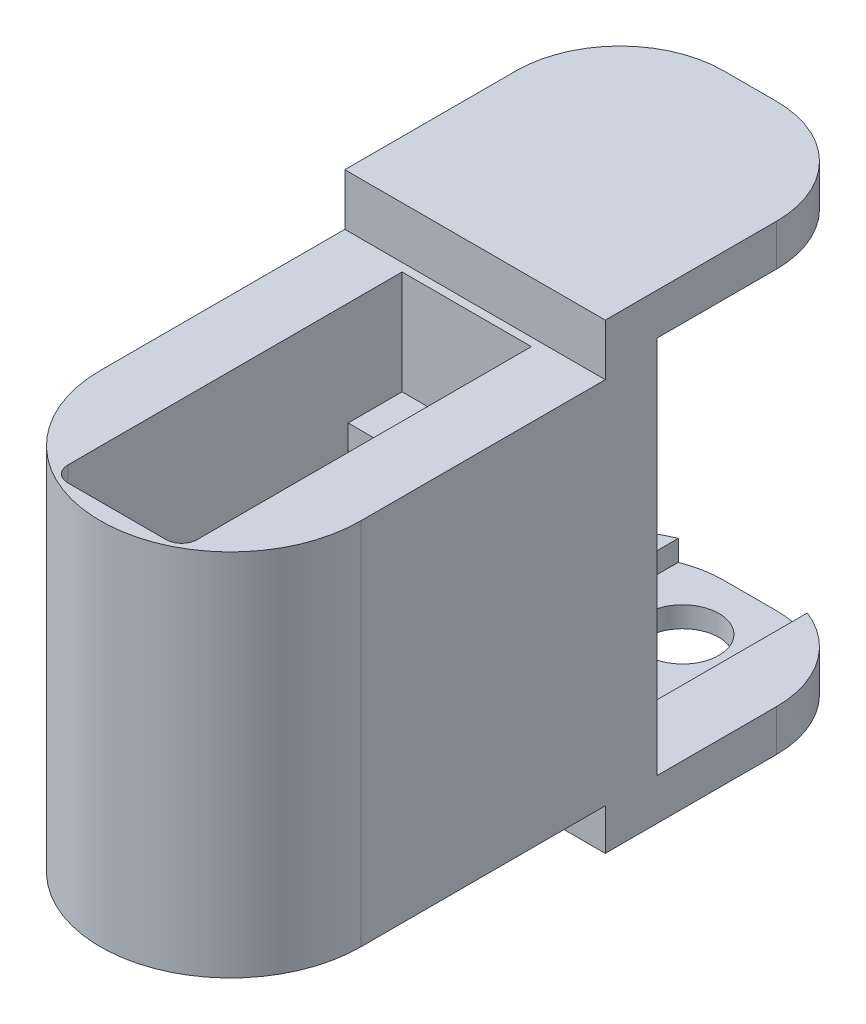
SolidWorks part; units mm, degrees
ref_plane "Front Plane" through (0, 0, 0) normal (0, 0, 1) x (1, 0, 0)
ref_plane "Top Plane" through (0, 0, 0) normal (0, 1, 0) x (1, 0, 0)
ref_plane "Right Plane" through (0, 0, 0) normal (1, 0, 0) x (0, 0, -1)
sketch "Sketch4" plane through (0, 0, 0) normal (0, 0, 1) x (1, 0, 0)
  line L1 (-6.23, -9.975) -> (6.23, -9.975)
  line L2 (-6.23, -9.975) -> (-6.23, 7.275)
  line L3 (-6.23, 7.275) -> (6.23, 7.275)
  line L4 (6.23, -9.975) -> (6.23, 7.275)
  point P4 (0, 7.275)
  dimension "D1" = 12.46
  dimension "D2" = 17.25
  dimension "D3" = 9.975
extrude "Boss-Extrude3" add sketch "Sketch4" along normal blind 6
sketch "Sketch8" plane through (0, -9.975, 0) normal (0, -1, 0) x (-1, 0, 0)
  circle A0 centre (0, -23.55) radius 12.5468
  circle A1 centre (0, -23.55) radius 11.15
  dimension "D1" = 22.3
  dimension "D2" = 23.55
extrude "Boss-Extrude6" add sketch "Sketch8" along normal blind 8.3 and the other way up to surface (17.25 mm away) other way up to face at (0, 7.275, 3)
sketch "Sketch5" plane through (0, 7.275, 0) normal (0, 1, 0) x (1, 0, 0)
  line L8 (12.5468, -23.55) -> (12.5468, 0)
  line L9 (12.5468, 0) -> (6.23, 0)
  line L10 (-12.5468, -23.55) -> (-12.5468, 0)
  line L11 (-12.5468, 0) -> (-6.23, 0)
  line L12 (-6.23, 0) -> (-6.23, -29.7)
  line L14 (6.23, -29.7) -> (6.23, 0)
  line L15 (-6.23, -29.7) -> (6.23, -29.7)
  line L16 (6.23, -6) -> (-6.23, -6) construction
  circle A0 centre (0, -23.55) radius 12.5468 construction
  arc A1 (-12.5468, -23.55) -> (12.5468, -23.55) centre (0, -23.55) ccw
  dimension "D1" = 23.7
  dimension "D2" = 23.55
extrude "Boss-Extrude4" add sketch "Sketch5" against normal up to surface (17.25 mm away) up to face at (0, -9.975, 3)
sketch "Sketch6" plane through (0, 7.275, 0) normal (0, 1, 0) x (1, 0, 0)
  line L0 (6.23, -6) -> (-6.23, -6) construction
  line L3 (6.23, -29.7) -> (-6.23, -29.7) construction
  circle A0 centre (0, -3.6) radius 0.75
  circle A1 centre (0, -32.1) radius 0.75
  dimension "D1" = 1.5
  dimension "D3" = 1.5
  dimension "D2" = 2.4
  dimension "D4" = 2.4
extrude "Cut-Extrude1" cut sketch "Sketch6" against normal blind 5
chamfer "Chamfer1" distance 0.5 angle 60 2 edges at (0, 7.275, 4.35) (0, 7.275, 32.85) first distance on face at (0, 7.275, 4.35)
sketch "Sketch10" plane through (0, 7.275, 0) normal (0, 1, 0) x (1, 0, 0)
  line L1 (-6.23, -6) -> (6.23, -6)
  line L2 (-6.23, -6) -> (-6.23, -29.7)
  line L3 (-6.23, -29.7) -> (6.23, -29.7)
  line L4 (6.23, -6) -> (6.23, -29.7)
extrude "Cut-Extrude3" cut sketch "Sketch10" against normal up to surface (17.25 mm away) up to face at (0, -9.975, 10.3399)
ref_plane "Plane1" through (0, 0, 36.0968) normal (0, 0, 1) x (1, 0, 0)
sketch "Sketch13" plane through (0, -18.275, 0) normal (0, -1, 0) x (1, 0, 0)
  line L0 (-12.5468, 23.55) -> (-12.5468, 0)
  line L1 (-12.5468, 0) -> (12.5468, 0)
  line L2 (12.5468, 0) -> (12.5468, 23.55)
  arc A0 (-12.5468, 23.55) -> (12.5468, 23.55) centre (0, 23.55) ccw
  point P3 (0, 0)
extrude "Boss-Extrude7" add sketch "Sketch13" against normal up to surface (8.3 mm away) up to face at (0, -9.975, 10.3399)
sketch "Sketch15" plane through (0, 7.275, 0) normal (0, 1, 0) x (1, 0, 0)
  line L0 (-12.5468, 0) -> (12.5468, 0)
  line L1 (12.5468, 0) -> (12.5468, -23.55)
  line L2 (-12.5468, 0) -> (-12.5468, -23.55)
  line L3 (6.23, -6) -> (6.23, -29.7) construction
  line L4 (-6.23, -0.8) -> (6.23, -0.8)
  line L5 (-6.23, -0.8) -> (-6.23, -33)
  line L6 (-4.73, -34.5) -> (4.73, -34.5)
  line L7 (6.23, -0.8) -> (6.23, -33)
  arc A0 (-12.5468, -23.55) -> (12.5468, -23.55) centre (0, -23.55) ccw
  circle A1 centre (0, -3.6) radius 0.75 construction
  arc A2 (4.73, -34.5) -> (6.23, -33) centre (4.73, -33) ccw
  arc A3 (-6.23, -33) -> (-4.73, -34.5) centre (-4.73, -33) ccw
  point P15 (0, -0.8)
  dimension "D1" = 0.8
  dimension "D3" = 1.5
  dimension "D2" = 2.8
  dimension "D4" = 0
  dimension "D5" = 34.5
extrude "Boss-Extrude9" add sketch "Sketch15" along normal blind 10
sketch "Sketch20" plane through (0, -18.275, 0) normal (0, -1, 0) x (1, 0, 0)
  circle A0 centre (0, 23.55) radius 7.15
  circle A1 centre (0, 23.55) radius 11.15
  circle A2 centre (0, 23.55) radius 11.15 construction
  dimension "D1" = 14.3
extrude "Boss-Extrude11" add sketch "Sketch20" against normal up to surface (8.3 mm away) up to face at (0, -9.975, 27.1007)
sketch "Sketch21" plane through (0, -18.275, 0) normal (0, -1, 0) x (1, 0, 0)
  circle A0 centre (0, 23.55) radius 7.15
  circle A1 centre (0, 23.55) radius 10.15
  circle A2 centre (0, 23.55) radius 7.15 construction
  dimension "D1" = 20.3
extrude "Cut-Extrude7" cut sketch "Sketch21" against normal blind 1.3
sketch "Sketch11" plane through (0, 0, 29.7) normal (0, 0, 1) x (1, 0, 0)
  line L1 (-5, -9.975) -> (5, -9.975)
  line L2 (-5, -9.975) -> (-5, -11.975)
  line L3 (-5, -11.975) -> (5, -11.975)
  line L4 (5, -9.975) -> (5, -11.975)
  line L5 (3.6469, -9.975) -> (6.23, -9.975) construction
  point P4 (0, -9.975)
  dimension "D1" = 0
  dimension "D2" = 10
  dimension "D3" = 2
extrude "Cut-Extrude4" cut sketch "Sketch11" against normal up to surface (23.7 mm away) up to face at (0, -1.35, 6)
sketch "Sketch17" plane through (-12.5468, 4.7282, 0) normal (1, 0, 0) x (0, -1, 0)
  line L0 (26.9782, 26.5) -> (26.9782, 0)
  line L1 (26.9782, 0) -> (-17.5218, 0)
  line L2 (-17.5218, 0) -> (-17.5218, 26.5)
  line L3 (-17.5218, 26.5) -> (-13.5218, 26.5)
  line L4 (-13.5218, 26.5) -> (-13.5218, 5)
  line L5 (-13.5218, 5) -> (22.9782, 5)
  line L6 (22.9782, 5) -> (22.9782, 26.5)
  line L7 (22.9782, 26.5) -> (26.9782, 26.5)
  point P2 (4.7282, 5)
  point P10 (4.7282, 0)
  dimension "D1" = 4
  dimension "D2" = 36.5
  dimension "D3" = 0
  dimension "D4" = 26.5
  dimension "D5" = 5
extrude "Boss-Extrude10" add sketch "Sketch17" along normal up to surface (25.0936 mm away) up to face at (12.5468, -0.5, 11.775)
sketch "Sketch18" plane through (0, -18.25, 0) normal (0, 1, 0) x (0, 0, 1)
  line L0 (-26.5, -12.5468) -> (-26.5, 12.5468) construction
  line L1 (-26.5, 6.2191) -> (-5, 6.2191)
  line L2 (-26.5, 6.2191) -> (-26.5, -6.2191)
  line L3 (-26.5, -6.2191) -> (-5, -6.2191)
  line L4 (-5, 6.2191) -> (-5, -6.2191)
  line L5 (-5, -12.5468) -> (-5, 12.5468) construction
  point P6 (-26.5, 0)
  point P7 (-26.5, 0)
  dimension "D1" = 0
extrude "Cut-Extrude5" cut sketch "Sketch18" against normal blind 2
sketch "Sketch19" plane through (0, -20.25, 0) normal (0, 1, 0) x (0, 0, 1)
  line L0 (-26.5, -12.5468) -> (-26.5, 12.5468) construction
  circle A0 centre (-20, 0) radius 3.5
  dimension "D1" = 7
  dimension "D2" = 6.5
extrude "Cut-Extrude6" cut sketch "Sketch19" against normal through all both and the other way through all
fillet "Fillet1" radius 10 4 edges at (12.5468, -20.25, -26.5) (-12.5468, -20.25, -26.5) (-12.5468, 20.25, -26.5) (12.5468, 20.25, -26.5)
ref_plane "Plane2" through (0, 0, 0) normal (1, 0, 0) x (0, 0, -1)
ref_plane "Plane3" through (0, -0.5, 0) normal (0, -1, 0) x (-1, 0, 0)
sketch "Sketch22" plane through (0, 22.25, 0) normal (0, 1, 0) x (1, 0, 0)
  circle A0 centre (0, 20) radius 6.5
  dimension "D1" = 13
extrude "Boss-Extrude12" add sketch "Sketch22" against normal blind 5
sketch "Sketch23" plane through (0, 17.25, 0) normal (0, -1, 0) x (1, 0, 0)
  circle A0 centre (0, -20) radius 5.85
  dimension "D1" = 11.7
extrude "Boss-Extrude13" add sketch "Sketch23" along normal blind 5
fillet "Fillet2" radius 1 1 edges at (0, 12.25, -25.85)
sketch "Sketch24" plane through (0, -18.275, 0) normal (0, -1, 0) x (1, 0, 0)
  line L0 (6.23, 20.0415) -> (6.23, 6) construction
  line L1 (-6.23, 6) -> (6.23, 6)
  line L2 (-6.23, 6) -> (-6.23, 11)
  line L3 (-6.23, 11) -> (6.23, 11)
  line L4 (6.23, 6) -> (6.23, 11)
  dimension "D1" = 5
extrude "Cut-Extrude8" cut sketch "Sketch24" against normal up to next
